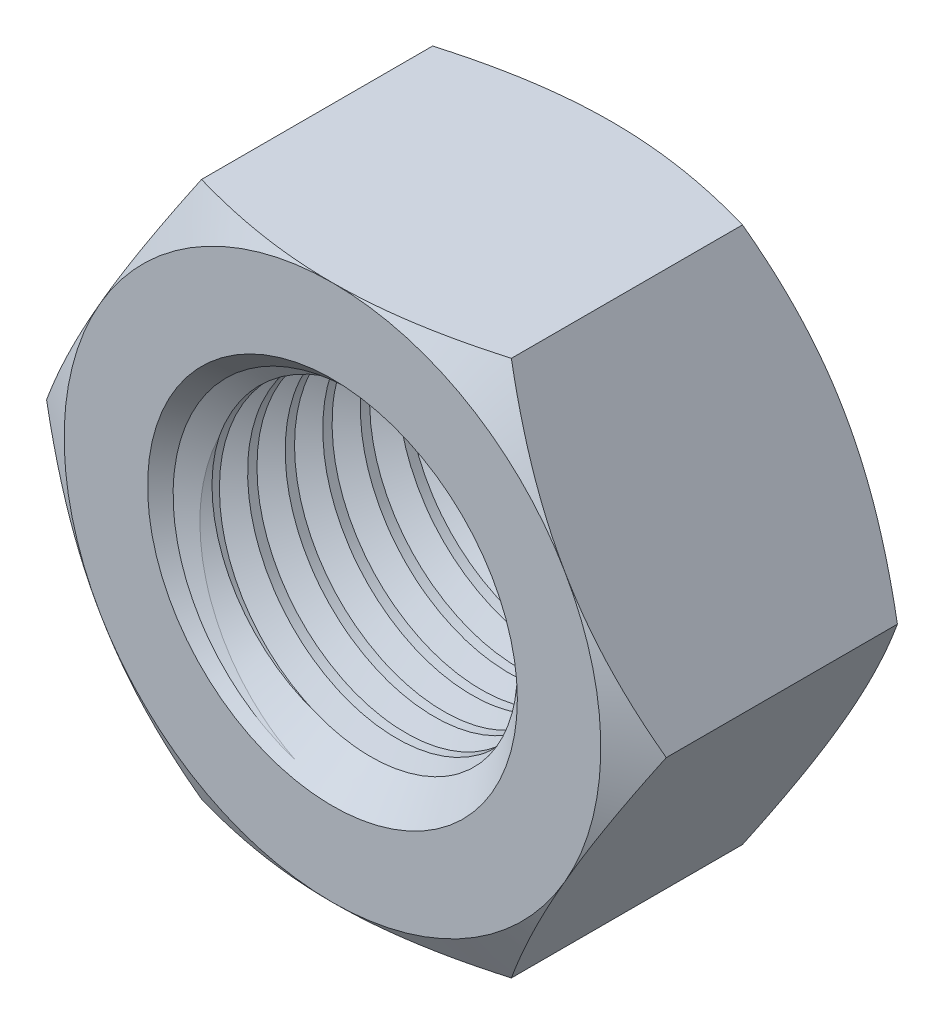
SolidWorks part; units mm, degrees
ref_plane "Front" through (0, 0, 0) normal (0, 0, 1) x (1, 0, 0)
ref_plane "Top" through (0, 0, 0) normal (0, 1, 0) x (1, 0, 0)
ref_plane "Right" through (0, 0, 0) normal (1, 0, 0) x (0, 0, -1)
sketch "Çizim1" plane through (0, 0, 0) normal (0, 0, 1) x (1, 0, 0)
  line L1 (28.8675, 0) -> (14.4338, 25)
  line L2 (14.4338, 25) -> (-14.4338, 25)
  line L3 (-14.4338, 25) -> (-28.8675, 0)
  line L4 (-28.8675, 0) -> (-14.4338, -25)
  line L5 (-14.4338, -25) -> (14.4338, -25)
  line L6 (14.4338, -25) -> (28.8675, 0)
  circle A0 centre (0, 0) radius 25 construction
  point P1 (0, 0)
  dimension "D1" = 50
extrude "Yükseklik-Ekstrüzyon1" add sketch "Çizim1" along normal blind 26
sketch "Çizim2" plane through (0, 0, 26) normal (0, 0, 1) x (1, 0, 0)
  circle A0 centre (0, 0) radius 25
extrude "Kes-Ekstrüzyon1" cut sketch "Çizim2" against normal blind 26 draft 60 flip side to cut
sketch "Çizim3" plane through (0, 0, 0) normal (0, 0, -1) x (-1, 0, 0)
  circle A0 centre (0, 0) radius 25
extrude "Kes-Ekstrüzyon2" cut sketch "Çizim3" against normal blind 26 draft 60 flip side to cut
sketch "Çizim4" plane through (0, 0, 26) normal (0, 0, 1) x (1, 0, 0)
  circle A0 centre (0, 0) radius 14.225
  dimension "D1" = 28.45
extrude "Kes-Ekstrüzyon3" cut sketch "Çizim4" against normal blind 26
chamfer "Pah1" distance 3 angle 45 2 edges at (14.225, 0, 0) (14.225, 0, 26)
sketch "Çizim5" plane through (0, 0, 0) normal (0, 0, -1) x (-1, 0, 0)
  circle A0 centre (0, 0) radius 14.225
curve "Helis/Spiral1" pitch 3.5 height 30 radius 14.225 centre (0, 0, 0) axis (0, 0, 1) start towards (-1, 0, 0)
ref_plane "Düzlem1" through (12.8163, 6.172, 30) normal (-0.4336, 0.9003, 0.0391) x (0.9011, 0.4331, 0.0188)
sketch "Çizim6" plane through (12.8163, 6.172, 30) normal (-0.4336, 0.9003, 0.0391) x (0.9011, 0.4331, 0.0188)
  line L0 (-0.7917, 1.7706) -> (-0.7917, -1.7706)
  line L1 (2.275, 0) -> (-0.7917, 1.7706)
  line L3 (-0.7917, -1.7706) -> (2.275, 0)
  line L5 (-1.1375, 1.9702) -> (-1.1375, 0) [skipped]
  circle A0 centre (0, 0) radius 1.1375 construction
  dimension "D1" = 2.275
sweep "Kes-Süpür1" cut profiles "Çizim6" path "Helis/Spiral1" align with end faces yes
